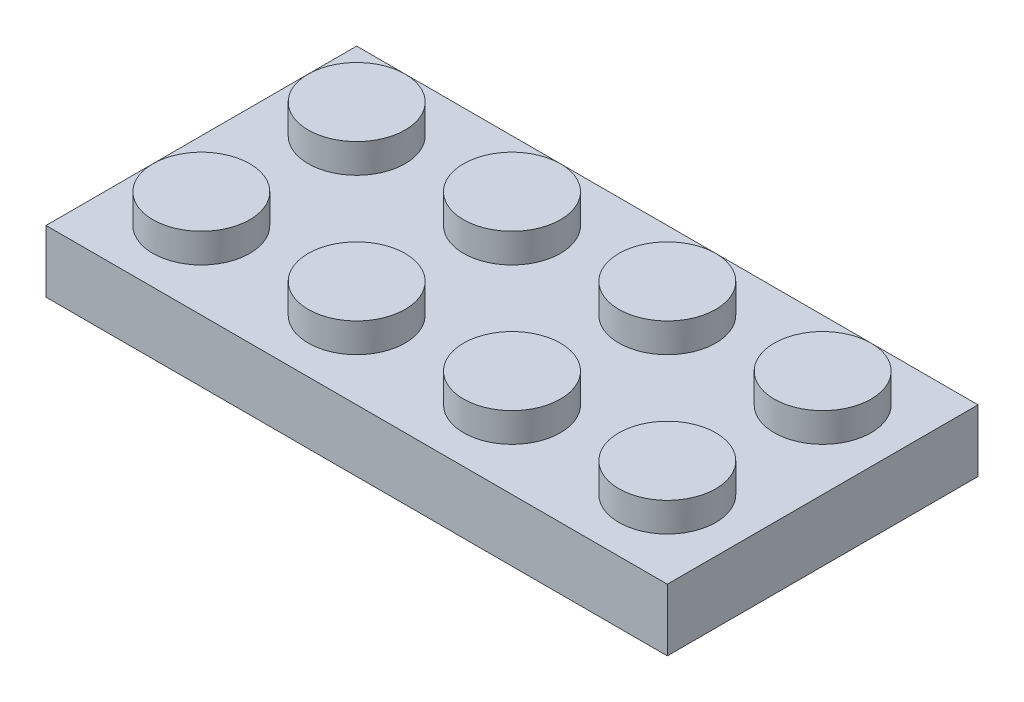
SolidWorks part; units mm, degrees
ref_plane "Front Plane" through (0, 0, 0) normal (0, 0, 1) x (1, 0, 0)
ref_plane "Top Plane" through (0, 0, 0) normal (0, 1, 0) x (1, 0, 0)
ref_plane "Right Plane" through (0, 0, 0) normal (1, 0, 0) x (0, 0, -1)
sketch "Sketch1" plane through (0, 0, 0) normal (0, 1, 0) x (1, 0, 0)
  line L1 (0, 0) -> (25.4, 0)
  line L2 (0, 0) -> (0, 12.7)
  line L3 (0, 12.7) -> (25.4, 12.7)
  line L4 (25.4, 0) -> (25.4, 12.7)
  circle A0 centre (3.175, 9.525) radius 1.9812
  dimension "D3" = 3.9624
  dimension "D1" = 25.4
  dimension "D2" = 12.7
  dimension "D4" = 3.175
  dimension "D5" = 3.175
extrude "Boss-Extrude1" add sketch "Sketch1" against normal blind 2.54 contours L1 L4 L3 L2
extrude "Boss-Extrude2" add sketch "Sketch1<3>" along normal blind 1.1938 contours A0 region at (3.175, 0, -9.525)
sketch "Sketch1<3>" plane through (0, 0, 0) normal (0, 1, 0) x (1, 0, 0) same geometry as "Sketch1"
pattern_linear "LPattern1" count 4 spacing 6.35 along (1, 0, 0) count 2 spacing 6.35 along (0, 0, 1) of "Boss-Extrude2"
shell "Shell1" thickness 1.1938 removed face at (12.7, -2.54, -6.35)
sketch "Sketch2" plane through (0, -1.1938, 0) normal (0, -1, 0) x (1, 0, 0)
  line L0 (0, 0) -> (0, -12.7) construction
  line L1 (0, 0) -> (25.4, 0) construction
  circle A0 centre (6.3379, -6.35) radius 1.9812
  circle A1 centre (6.3379, -6.35) radius 2.5019
  point P5 (0, -6.35)
  dimension "D1" = 3.9624
  dimension "D2" = 5.0038
  dimension "D3" = 6.3379
  dimension "D4" = 6.35
extrude "Boss-Extrude3" add sketch "Sketch2" along normal up to surface (1.3462 mm away) up to face at (12.7, -2.54, -6.35)
pattern_linear "LPattern2" count 3 spacing 6.35 along (1, 0, 0) of "Boss-Extrude3"
fillet "Fillet1" radius 1.1938 4 edges at (24.2062, -1.8669, -11.5062) (1.1938, -1.8669, -11.5062) (1.1938, -1.8669, -1.1938) (24.2062, -1.8669, -1.1938)
